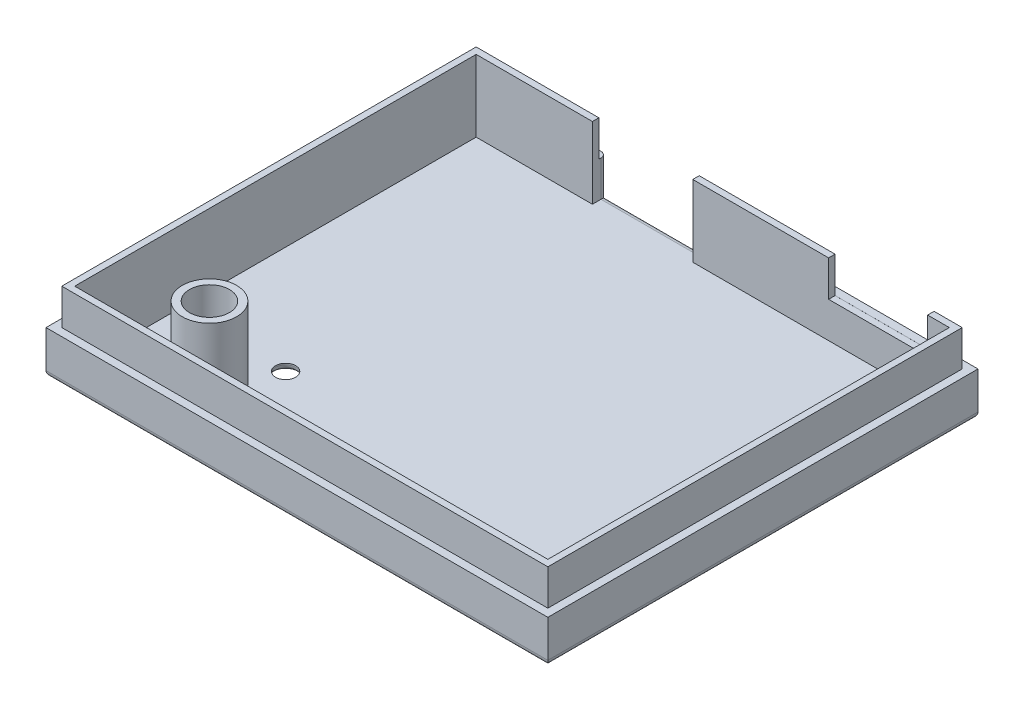
SolidWorks part; units mm, degrees
ref_plane "Front Plane" through (0, 0, 0) normal (0, 0, 1) x (1, 0, 0)
ref_plane "Top Plane" through (0, 0, 0) normal (0, 1, 0) x (1, 0, 0)
ref_plane "Right Plane" through (0, 0, 0) normal (1, 0, 0) x (0, 0, -1)
sketch "Sketch1" plane through (0, 0, 0) normal (0, 1, 0) x (1, 0, 0)
  line L1 (0, 0) -> (70, 0)
  line L2 (0, 0) -> (0, 60)
  line L3 (0, 60) -> (70, 60)
  line L4 (70, 0) -> (70, 60)
  dimension "D1" = 60
  dimension "D2" = 70
extrude "Boss-Extrude1" add sketch "Sketch1" along normal blind 1
sketch "Sketch2" plane through (0, 1, 0) normal (0, 1, 0) x (1, 0, 0)
  line L14 (2, 58) -> (2, 2)
  line L15 (0, 60) -> (70, 60)
  line L16 (0, 60) -> (0, 0)
  line L17 (0, 0) -> (70, 0)
  line L22 (70, 60) -> (70, 0)
  line L23 (2, 2) -> (68, 2)
  line L24 (68, 58) -> (68, 2)
  line L25 (2, 58) -> (68, 58)
extrude "Boss-Extrude3" add sketch "Sketch2" along normal blind 5
sketch "Sketch3" plane through (0, 0, 0) normal (0, -1, 0) x (1, 0, 0)
  line L0 (17.0123, -17.9087) -> (17.0123, -14.9115) construction
  line L1 (9.3873, -17.9087) -> (9.3873, -14.9115) construction
  circle A0 centre (17.0123, -16.4101) radius 1.4
  circle A1 centre (9.3873, -16.4101) radius 1.4
  dimension "D1" = 2.8
extrude "Cut-Extrude1" cut sketch "Sketch3" against normal up to next
sketch "Sketch4" plane through (0, 0, 0) normal (0, -1, 0) x (-1, 0, 0)
  circle A0 centre (-13.2, 9.6) radius 1.7903
  dimension "D1" = 3.5807
extrude "Cut-Extrude2" cut sketch "Sketch4" against normal up to next
sketch "Sketch5" plane through (0, 1, 0) normal (0, 1, 0) x (1, 0, 0)
  circle A0 centre (13.2, 9.6) radius 2.7903
  circle A3 centre (13.2, 9.6) radius 1.7903 construction
  circle A4 centre (13.2, 9.6) radius 3.7903
  dimension "D1" = 1
  dimension "D2" = 1
extrude "Boss-Extrude4" add sketch "Sketch5" along normal blind 10
sketch "Sketch6" plane through (0, 0, -60) normal (0, 0, -1) x (-1, 0, 0)
  line L0 (-70, 6) -> (0, 6) construction
  line L1 (-18.2149, 6) -> (-32.2149, 6)
  line L2 (-18.2149, 6) -> (-18.2149, 1)
  line L3 (-18.2149, 1) -> (-32.2149, 1)
  line L4 (-32.2149, 6) -> (-32.2149, 1)
  line L5 (-31.2149, 1.9585) -> (-31.2149, 4.2085) construction
  line L6 (-18.7149, 3.5085) -> (-18.7149, 4.5085) construction
  line L7 (-68, 1) -> (-2, 1) construction
  dimension "D1" = 1
  dimension "D3" = 0.5
extrude "Cut-Extrude3" cut sketch "Sketch6" against normal up to next
sketch "Sketch8" plane through (0, 6, 0) normal (0, 1, 0) x (1, 0, 0)
  line L0 (1.1, 58.9) -> (1.1, 1.1)
  line L1 (2, 58) -> (68, 58)
  line L2 (2, 58) -> (2, 2)
  line L3 (2, 2) -> (68, 2)
  line L4 (68, 58) -> (68, 2)
  line L5 (1.1, 1.1) -> (68.9, 1.1)
  line L6 (68.9, 58.9) -> (68.9, 1.1)
  line L7 (1.1, 58.9) -> (68.9, 58.9)
  dimension "D1" = 0.9
extrude "Boss-Extrude5" add sketch "Sketch8" along normal blind 5
sketch "Sketch9" plane through (0, 0, -58) normal (0, 0, 1) x (1, 0, 0)
  line L0 (68, 11) -> (2, 11) construction
  line L2 (18.2149, 6) -> (32.2149, 6)
  line L3 (18.2149, 6) -> (18.2149, 11)
  line L4 (18.2149, 11) -> (32.2149, 11)
  line L5 (32.2149, 6) -> (32.2149, 11)
extrude "Cut-Extrude6" cut sketch "Sketch9" against normal up to next
sketch "Sketch10" plane through (0, 0, -58.9) normal (0, 0, -1) x (-1, 0, 0)
  line L0 (-64.674, 17.954) -> (-64.674, 6.2954) construction
  line L1 (-51.466, 6.2954) -> (-64.674, 6.2954)
  line L2 (-51.466, 6.2954) -> (-51.466, 11)
  line L3 (-51.466, 11) -> (-64.674, 11)
  line L4 (-64.674, 6.2954) -> (-64.674, 11)
  line L5 (-68.9, 11) -> (-32.2149, 11) construction
  line L6 (-51.166, 5.9954) -> (-51.166, 11.3)
  line L7 (-51.166, 11.3) -> (-64.974, 11.3)
  line L8 (-64.974, 5.9954) -> (-64.974, 11.3)
  line L9 (-51.166, 5.9954) -> (-64.974, 5.9954)
extrude "Cut-Extrude7" cut sketch "Sketch10" against normal up to next
sketch "Sketch12" plane through (0, 0, 0) normal (0, -1, 0) x (-1, 0, 0)
  line L0 (-8.632, 30) -> (-61.368, 30) construction
  line L1 (-5.8873, 21.4101) -> (-12.8873, 21.4101) construction
  line L2 (-9.3873, 16.4101) -> (-17.0123, 16.4101) construction
  line L3 (-13.5123, 21.4101) -> (-20.5123, 21.4101) construction
  line L4 (-9.3873, 21.4101) -> (-17.0123, 21.4101) construction
  line L16 (-70, 60) -> (0, 0) construction
  line L17 (-70, 0) -> (0, 60) construction
  circle A0 centre (-9.3873, 16.4101) radius 1.4 construction
  text T0 "Twomes Gateway V1" font "@Microsoft JhengHei UI" height 3.5
  text T1 "Led1" font "Century Gothic" height 3.5
  text T2 "Led2" font "Century Gothic" height 3.5
  point P11 (-13.1998, 16.4101)
  point P21 (-13.1998, 21.4101)
  point P22 (-35, 30)
  point P23 (-35, 30)
  dimension "D1" = 5
  dimension "D2" = 7
extrude "Cut-Extrude9" cut sketch "Sketch12" against normal blind 0.3
fillet "Fillet2" radius 0.8 4 edges at (70, 0, -30) (35, 0, 0) (0, 0, -30) (35, 0, -60)
fillet "Fillet3" radius 0.8 3 edges at (32.2149, 3.5, -60) (18.2149, 3.5, -60) (25.2149, 1, -60)
fillet "Fillet4" radius 0.8 2 edges at (9.3873, 0, -17.8101) (17.0123, 0, -17.8101)
equation "\"assembly_offset\"= 0.3mm"
equation "\"case_thickness\"= 1mm"
equation "\"case_length\"= 60mm"
equation "\"case_width\"= 70mm"
equation "\"D1@Sketch1\"=\"case_length\""
equation "\"D2@Sketch1\"=\"case_width\""
equation "\"D1@Boss-Extrude1\"=\"case_thickness\""
equation "\"D1@Sketch2\"=\"case_thickness\"*2"
equation "\"case_height\"= 5mm"
equation "\"D1@Boss-Extrude3\"=\"case_height\""
equation "\"D1@Sketch4\"=\"assembly_offset\"+2.98069177+0.3"
equation "\"D1@Sketch3\"=\"assembly_offset\"+2.50"
equation "\"case_connect_wall\"= 5mm"
equation "\"D1@Boss-Extrude5\"=\"case_connect_wall\""
equation "\"D1@Sketch10\"=\"assembly_offset\""
equation "\"D1@Sketch8\"=\"case_thickness\"-\"connect_wall_assembly_offset\""
equation "\"connect_wall_assembly_offset\"= 0.1mm"
equation "\"fillet_topbottom\"= 0.8mm"
equation "\"D1@Fillet2\"=\"fillet_topbottom\""
equation "\"D1@Fillet3\"=\"fillet_topbottom\""
equation "\"D1@Fillet4\"=\"fillet_topbottom\""
